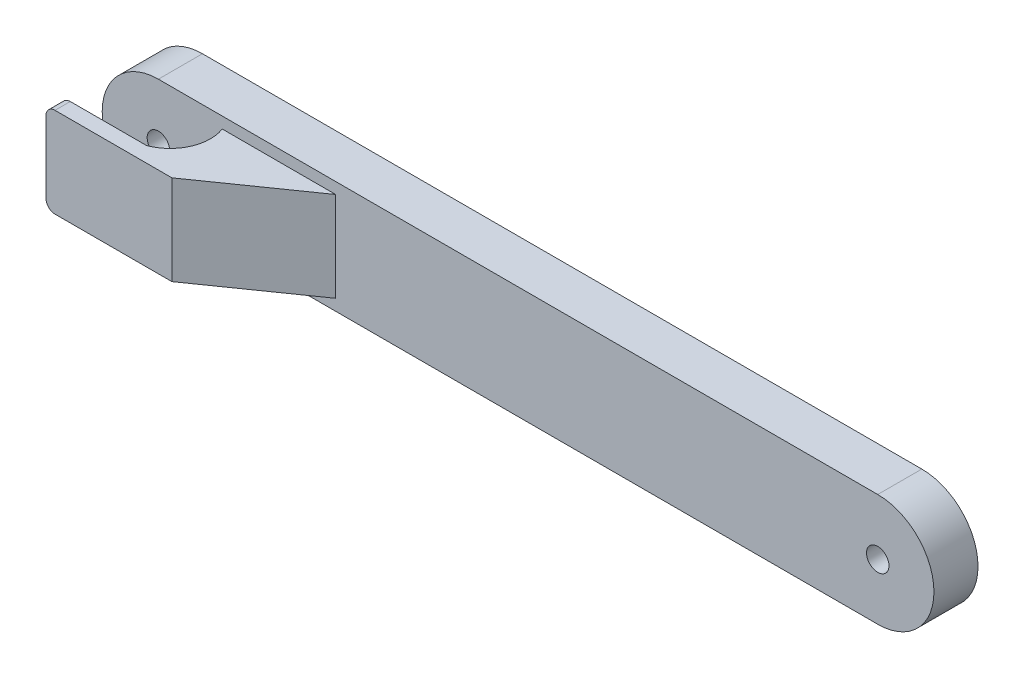
SolidWorks part; units mm, degrees
ref_plane "Front" through (0, 0, 0) normal (0, 0, 1) x (1, 0, 0)
ref_plane "Top" through (0, 0, 0) normal (0, 1, 0) x (1, 0, 0)
ref_plane "Right" through (0, 0, 0) normal (1, 0, 0) x (0, 0, -1)
sketch "Sketch1" plane through (0, 0, 0) normal (0, 0, 1) x (1, 0, 0)
  line L0 (299.8703, -79.0606) -> (503.0703, -79.0606) construction
  line L1 (299.8703, -63.1856) -> (503.0703, -63.1856)
  line L2 (299.8703, -94.9356) -> (503.0703, -94.9356)
  line L3 (401.4703, -94.9356) -> (401.4703, -63.1856) construction
  arc A0 (299.8703, -63.1856) -> (299.8703, -94.9356) centre (299.8703, -79.0606) ccw
  arc A1 (503.0703, -94.9356) -> (503.0703, -63.1856) centre (503.0703, -79.0606) ccw
  circle A2 centre (299.8703, -79.0606) radius 3.175
  circle A3 centre (503.0703, -79.0606) radius 3.175
  point P2 (401.4703, -79.0606)
  dimension "D1" = 203.2
  dimension "D2" = 15.875
  dimension "D3" = 31.75
extrude "Boss-Extrude1" add sketch "Sketch1" along normal blind 12.446
sketch "Sketch2" plane through (0, 0, 0) normal (0, 0, -1) x (-1, 0, 0)
  line L5 (-477.6703, -66.3606) -> (-477.6703, -91.7606)
  line L6 (-513.2303, -91.7606) -> (-477.6703, -91.7606)
  line L7 (-515.7703, -89.2206) -> (-515.7703, -68.9006)
  line L8 (-513.2303, -66.3606) -> (-477.6703, -66.3606)
  line L10 (-515.7703, -91.7606) -> (-490.3703, -66.3606) construction
  line L11 (-515.7703, -66.3606) -> (-490.3703, -91.7606) construction
  arc A0 (-513.2303, -91.7606) -> (-515.7703, -89.2206) centre (-513.2303, -89.2206) cw
  arc A3 (-515.7703, -68.9006) -> (-513.2303, -66.3606) centre (-513.2303, -68.9006) cw
  point P0 (-503.0703, -79.0606)
  dimension "D3" = 2.54
  dimension "D1" = 25.4
  dimension "D2" = 25.4
  dimension "D4" = 35.56
ref_plane "Plane5" through (401.447, 0, 0) normal (1, 0, 0) x (0, 0, -1)
surface "Surface-MidSurface2" parameters "D0"=50000
sketch "Sketch7" plane through (0, 0, 12.446) normal (0, 0, 1) x (1, 0, 0)
  line L0 (310.0303, -66.3606) -> (312.5703, -66.3606)
  line L1 (289.7103, -91.7606) -> (310.0303, -91.7606)
  line L2 (287.1703, -89.2206) -> (287.1703, -68.9006)
  line L3 (289.7103, -66.3606) -> (310.0303, -66.3606)
  line L5 (287.1703, -91.7606) -> (312.5703, -66.3606) construction
  line L6 (287.1703, -66.3606) -> (312.5703, -91.7606) construction
  line L7 (312.5703, -66.3606) -> (322.7303, -66.3606)
  line L8 (322.7303, -66.3606) -> (322.7303, -91.7606)
  line L9 (310.0303, -91.7606) -> (322.7303, -91.7606)
  arc A0 (289.7103, -91.7606) -> (287.1703, -89.2206) centre (289.7103, -89.2206) cw
  arc A3 (287.1703, -68.9006) -> (289.7103, -66.3606) centre (289.7103, -68.9006) cw
  point P0 (299.8703, -79.0606)
  dimension "D3" = 2.54
  dimension "D1" = 25.4
  dimension "D2" = 25.4
  dimension "D4" = 10.16
extrude "Boss-Extrude8" add sketch "Sketch7" along normal blind 19.05
sketch "Sketch8" plane through (0, -66.3606, 0) normal (0, 1, 0) x (1, 0, 0)
  line L0 (287.1703, -12.446) -> (317.9043, -12.446)
  line L1 (503.0703, -12.446) -> (299.8703, -12.446) construction
  line L2 (287.1703, -12.446) -> (287.1703, -27.178)
  line L3 (287.1703, -31.496) -> (287.1703, -12.446) construction
  line L4 (287.1703, -27.178) -> (311.3003, -27.178)
  arc A0 (317.9043, -12.446) -> (311.3003, -27.178) centre (307.218, -16.5018) cw
  dimension "D1" = 30.734
  dimension "D2" = 14.732
  dimension "D3" = 24.13
extrude "Cut-Extrude3" cut sketch "Sketch8" against normal blind 41.148
sketch "Sketch9" plane through (0, -66.3606, 0) normal (0, 1, 0) x (1, 0, 0)
  line L0 (322.7303, -31.496) -> (349.9365, -12.446)
  line L1 (503.0703, -12.446) -> (299.8703, -12.446) construction
  line L4 (322.7303, -12.446) -> (349.9365, -12.446)
  line L5 (322.7303, -31.496) -> (322.7303, -12.446)
  dimension "D1" = 35
extrude "Boss-Extrude9" add sketch "Sketch9" against normal blind 25.4
